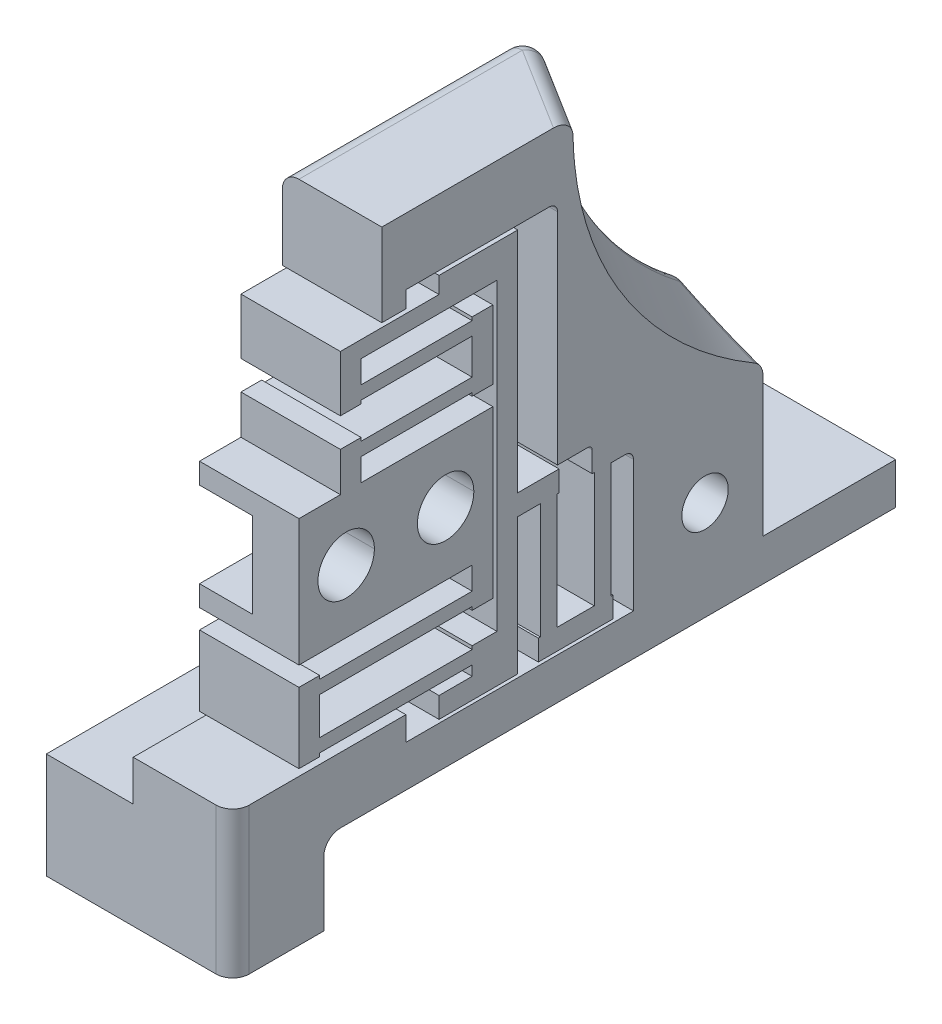
SolidWorks part; units mm, degrees
other "Markup1"
sketch "Sketch8" plane through (10.5, 0, 3) normal (0.7095, 0.0467, 0.7031) x (0.7044, -0.0184, -0.7096)
ref_plane "Front Plane" through (0, 0, 0) normal (0, 0, 1) x (1, 0, 0)
ref_plane "Top Plane" through (0, 0, 0) normal (0, 1, 0) x (1, 0, 0)
ref_plane "Right Plane" through (0, 0, 0) normal (1, 0, 0) x (0, 0, -1)
sketch "Sketch1" plane through (0, 0, 0) normal (1, 0, 0) x (0, 0, -1)
  line L0 (-1.25, -12.7333) -> (6.7, -12.7333)
  line L1 (6.7, -12.7333) -> (6.7, -22.75)
  line L2 (-5, -12.7333) -> (-5, -20.3833)
  line L3 (-5, -20.3833) -> (5.45, -20.3833)
  line L57 (-3.75, -22.55) -> (-3.75, -24.8)
  line L58 (-3.75, -24.8) -> (5.45, -24.8)
  line L60 (5.45, -20.3833) -> (5.45, -21.75)
  line L62 (-5, -21.55) -> (-5, -25.8)
  line L64 (6.95, -6.25) -> (6.95, -24.6)
  line L65 (-1.25, -11.3667) -> (5.45, -11.3667)
  line L66 (5.45, -10.5667) -> (5.45, -8.4167)
  line L68 (-2.5, -8.6167) -> (-2.5, -5.25)
  line L69 (-1.25, -12.7333) -> (-1.25, -11.3667)
  line L71 (6.7, -11.5667) -> (6.7, -7.4167)
  line L73 (-1.25, -7.6167) -> (-1.25, -6.25)
  line L74 (-1.25, -6.25) -> (6.95, -6.25)
  line L75 (-2.5, -5.25) -> (3.45, -5.25)
  line L79 (5.45, -11.3667) -> (5.45, -11.5667)
  line L80 (5.45, -11.5667) -> (6.7, -11.5667)
  line L85 (5.45, -10.5667) -> (-1.25, -10.5667)
  line L86 (-1.25, -10.5667) -> (-1.25, -10.3667)
  line L87 (-1.25, -10.3667) -> (-2.5, -10.3667)
  line L90 (5.45, -8.4167) -> (-1.25, -8.4167)
  line L91 (-1.25, -8.4167) -> (-1.25, -8.6167)
  line L92 (-1.25, -8.6167) -> (-2.5, -8.6167)
  line L93 (-1.25, -7.6167) -> (5.45, -7.6167)
  line L98 (5.45, -7.6167) -> (5.45, -7.4167)
  line L99 (5.45, -7.4167) -> (6.7, -7.4167)
  line L102 (5.45, -21.75) -> (-3.75, -21.75)
  line L103 (-3.75, -21.75) -> (-3.75, -21.55)
  line L104 (-3.75, -21.55) -> (-5, -21.55)
  line L105 (6.7, -22.75) -> (5.45, -22.75)
  line L106 (5.45, -22.75) -> (5.45, -22.55)
  line L111 (5.45, -22.55) -> (-3.75, -22.55)
  line L115 (5.45, -24.8) -> (5.45, -24.6)
  line L116 (5.45, -24.6) -> (6.95, -24.6)
  line L117 (-5, -25.8) -> (-3.75, -25.8)
  line L118 (-3.75, -25.8) -> (-3.75, -25.6)
  line L119 (-3.75, -25.6) -> (5.45, -25.6)
  line L124 (5.45, -25.6) -> (5.45, -26.2)
  line L126 (5.45, -26.2) -> (3.45, -26.2)
  line L127 (3.45, -26.2) -> (3.45, -27.45)
  line L128 (3.45, -27.45) -> (8.2, -27.45)
  line L130 (12.8167, -26.2) -> (10.5667, -26.2)
  line L131 (10.5667, -26.2) -> (10.5667, -19.2333)
  line L136 (10.5667, -19.2333) -> (10.6917, -19.2333)
  line L141 (12.8167, -19.2333) -> (12.8167, -26.2)
  line L145 (9.5667, -26.2) -> (9.4417, -26.2)
  line L146 (9.5667, -26.2) -> (9.5667, -19.2333)
  line L150 (9.5667, -19.2333) -> (8.2, -19.2333)
  line L153 (8.2, -17.9833) -> (10.6917, -17.9833)
  line L155 (14.6833, -19.2333) -> (13.8167, -19.2333)
  line L160 (13.8167, -19.2333) -> (13.8167, -26.2)
  line L168 (15.1833, -27.7) -> (15.1833, -19.7333)
  line L179 (15.1833, -27.7) -> (1.45, -27.7)
  line L180 (1.45, -27.7) -> (1.45, -26.2)
  line L181 (1.45, -26.2) -> (-9, -26.2)
  line L184 (-9, -30.15) -> (23, -30.15)
  line L187 (23, 0) -> (0, 0)
  line L189 (8.2, -27.45) -> (8.2, -19.2333)
  line L190 (1.45, -5) -> (0, -5)
  line L191 (0, -5) -> (0, 0)
  line L192 (13.9417, -26.2) -> (13.8167, -26.2)
  line L193 (12.4417, -17.7333) -> (10.6, -17.7333)
  line L194 (10.6, -17.7333) -> (10.6, -4.5)
  line L198 (9.4417, -26.2) -> (9.4417, -27.45)
  line L199 (13.9417, -26.2) -> (13.9417, -27.45)
  line L200 (13.9417, -27.45) -> (9.4417, -27.45)
  line L201 (8.2, -17.9833) -> (8.2, -4.25)
  line L203 (12.6917, -19.2333) -> (12.6917, -17.9833)
  line L204 (10.6917, -19.2333) -> (10.6917, -17.9833)
  line L205 (12.6917, -19.2333) -> (12.8167, -19.2333)
  line L212 (-9, -30.15) -> (-9, -26.2)
  line L214 (-2.5, -12.7333) -> (-5, -12.7333)
  line L215 (-2.5, -12.7333) -> (-2.5, -10.3667)
  line L216 (23, 0) -> (23, -30.15)
  line L217 (1.45, -5) -> (1.45, -4)
  line L218 (1.45, -4) -> (10.1, -4)
  line L219 (3.45, -5.25) -> (3.45, -4.25)
  line L220 (3.45, -4.25) -> (8.2, -4.25)
  line L221 (13.8167, -19.2333) -> (15.1833, -19.2333) construction
  arc A4 (14.6833, -19.2333) -> (15.1833, -19.7333) centre (14.6833, -19.7333) cw
  arc A5 (12.6917, -17.9833) -> (12.4417, -17.7333) centre (12.4417, -17.9833) ccw
  arc A6 (10.1, -4) -> (10.6, -4.5) centre (10.1, -4.5) cw
  circle A7 centre (3.85, -16.5583) radius 1.7
  circle A8 centre (-2.15, -16.5583) radius 1.7
  circle A9 centre (-2.15, -16.5583) radius 2.85 construction
  circle A10 centre (3.85, -16.5583) radius 2.85 construction
  point P120 (10.6, -5)
  point P140 (15.1833, -19.2333)
  point P144 (12.6917, -17.7333)
  point P151 (-5, -16.5583)
  point P159 (-1.875, -8.6167)
  dimension "D61" = 0.5
  dimension "D62" = 0.25
  dimension "D66" = 0.5
  dimension "D67" = 3.4
  dimension "D68" = 5.7
  dimension "D3" = 4.25
  dimension "D4" = 0.2
  dimension "D6" = 0.8
  dimension "D9" = 0.8
  dimension "D10" = 1.1667
  dimension "D17" = 0.8
  dimension "D18" = 1.75
  dimension "D21" = 0.8
  dimension "D23" = 1
  dimension "D24" = 0.25
  dimension "D37" = 1.25
  dimension "D40" = 0.25
  dimension "D44" = 1
  dimension "D12" = 7.65
  dimension "D20" = 1.25
  dimension "D26" = 1.25
  dimension "D28" = 0.25
  dimension "D33" = 1.25
  dimension "D49" = 2.4
  dimension "D50" = 0.25
  dimension "D31" = 5
  dimension "D54" = 5
  dimension "D55" = 1.25
  dimension "D65" = 2.5
  dimension "D64" = 2.5
  dimension "D29" = 2
  dimension "D52" = 0.25
  dimension "D56" = 1
  dimension "D69" = 6
  dimension "D39" = 4
  dimension "D51" = 32
  dimension "D22" = 1.1667
  dimension "D53" = 2
  dimension "D19" = 0.2
  dimension "D7" = 0.4
  dimension "D8" = 1.45
  dimension "D11" = 1
  dimension "D13" = 4.5
  dimension "D14" = 2
  dimension "D15" = 30.15
  dimension "D16" = 1.25
  dimension "D25" = 1.25
extrude "Boss-Extrude1" add sketch "Sketch1" along normal blind 6
sketch "Sketch2" plane through (0, 0, 5) normal (0, 0, 1) x (1, 0, 0)
  line L0 (6, -12.7333) -> (6, -20.3833) construction
  line L1 (6, -19.1333) -> (2.8, -19.1333)
  line L2 (6, -19.1333) -> (6, -13.9833)
  line L3 (6, -13.9833) -> (2.8, -13.9833)
  line L4 (2.8, -19.1333) -> (2.8, -13.9833)
  line L5 (6, -12.7333) -> (6, -20.3833) construction
  dimension "D1" = 3.2
  dimension "D2" = 1.25
  dimension "D3" = 1.25
extrude "Cut-Extrude4" cut sketch "Sketch2" against normal up to next
sketch "Sketch3" plane through (0, -30.15, 0) normal (0, -1, 0) x (1, 0, 0)
  line L0 (11.24, -4.18) -> (16.24, -4.18)
  line L1 (0, -31) -> (16.24, -31)
  line L2 (0, -31) -> (0, 9)
  line L4 (11.24, -4.18) -> (11.24, 9)
  line L5 (6, 9) -> (6, -23) construction
  line L7 (16.24, -31) -> (16.24, -4.18)
  line L8 (0, 9) -> (0, -23) construction
  line L9 (11.24, 9) -> (0, 9)
  circle A0 centre (8.6, -7.73) radius 1.6
  circle A1 centre (8.6, -19.73) radius 1.6
  dimension "D3" = 3.2
  dimension "D1" = 13.18
  dimension "D2" = 2.6
  dimension "D4" = 12
  dimension "D5" = 5
  dimension "D6" = 40
  dimension "D7" = 16.73
  dimension "D8" = 11.24
sketch "Sketch7" plane through (0, 0, 0) normal (-1, 0, 0) x (0, 0, 1)
  line L0 (2.5, -12.7333) -> (5, -12.7333) construction
  line L2 (-6.7, -12.7333) -> (-6.7, -22.75) construction
  circle A0 centre (2.15, -16.6083) radius 1.7
  circle A1 centre (-3.85, -16.6083) radius 1.7
  circle A2 centre (2.15, -16.6083) radius 2.85 construction
  circle A3 centre (-3.85, -16.6083) radius 2.85 construction
  dimension "D1" = 3.4
  dimension "D2" = 3.875
  dimension "D5" = 5.7
  dimension "D3" = 6
extrude "Cut-Extrude3" cut sketch "Sketch7" against normal up to next
extrude "Boss-Extrude2" add sketch "Sketch3" against normal blind 2.5
sketch "Sketch12" plane through (0, 0, 9) normal (0, 0, 1) x (1, 0, 0)
  line L0 (6, -26.2) -> (6, -27.65) construction
  line L1 (11.24, -27.65) -> (6, -27.65)
  line L2 (11.24, -27.65) -> (11.24, -28.65)
  line L3 (11.24, -28.65) -> (6, -28.65)
  line L4 (6, -27.65) -> (6, -28.65)
  line L5 (11.24, -27.65) -> (6, -27.65) construction
  dimension "D1" = 1
  dimension "D2" = 5.24
extrude "Cut-Extrude6" cut sketch "Sketch12" against normal blind 35.15
sketch "Sketch14" plane through (0, 0, 0) normal (-1, 0, 0) x (0, 0, 1)
  line L1 (9, -28.7) -> (3.5, -28.7)
  line L2 (9, -28.7) -> (9, -35.03)
  line L3 (9, -35.03) -> (3.5, -35.03)
  line L4 (3.5, -28.7) -> (3.5, -35.03)
  line L5 (-1.45, -26.2) -> (9, -26.2) construction
  line L6 (9, -26.2) -> (9, -30.15) construction
  dimension "D1" = 2.5
  dimension "D2" = 6.33
  dimension "D3" = 5.5
extrude "Boss-Extrude4" add sketch "Sketch14" against normal blind 11.24
sketch "Sketch15" plane through (11.24, 0, 0) normal (1, 0, 0) x (0, 0, -1)
  line L1 (-3.5, -30.15) -> (-7.5, -30.15)
  line L2 (-3.5, -30.15) -> (-3.5, -33.48)
  line L3 (-3.5, -33.48) -> (-7.5, -33.48)
  line L4 (-7.5, -30.15) -> (-7.5, -33.48)
  dimension "D1" = 4
  dimension "D2" = 3.33
extrude "Cut-Extrude7" cut sketch "Sketch15" against normal blind 10.25
ref_plane "Plane2" through (0, 0, 7.1) normal (0, 0, 1) x (1, 0, 0)
ref_axis "Axis1" through (11.24, 27.1504, 7.1) along (0, -1, 0)
mirror "Mirror1" [suppressed] of bodies 111
delete or keep bodies "Body-Delete/Keep 1" [suppressed] type delete bodies bodies 111
ref_plane "Plane1" through (4.8929, 0, -3.0574) normal (-0.848, 0, 0.5299) x (0, -1, 0)
sketch "Sketch10" plane through (4.8929, 0, -3.0574) normal (-0.848, 0, 0.5299) x (0, -1, 0)
  line L0 (30.15, 13.5887) -> (30.15, 7.6324) construction
  line L1 (30.15, 2.9682) -> (30.15, -26.2895) construction
  line L2 (30.15, 12.3167) -> (30.15, -33.4435) construction
  circle A0 centre (0.65, -31.2799) radius 21.5
  dimension "D2" = 43
  dimension "D1" = 43.5966
  dimension "D3" = 29.5
extrude "Cut-Extrude5" cut sketch "Sketch10" against normal blind 25
fillet "Fillet1" radius 1 9 edges at (3.1138, -17.4436, -23) (3, 0, -13.4184) (6, -21.8736, -23) (6, -8.7382, -17.1438) (6, 0, -7.6465) (16.24, -28.9, -4.18) (0.99, -31.815, 7.5) (0, -30.615, 9) (0.495, -30.15, 3.5)
chamfer "Chamfer1" distance 1 angle 45 1 edges at (11.24, -27.65, -15.165)
delete or keep bodies "Body-Delete/Keep 2" [suppressed] type delete bodies bodies 113
sketch "Sketch16" plane through (0, 0, 0) normal (-1, 0, 0) x (0, 0, 1)
  line L0 (-23, -27.65) -> (-31, -27.65) construction
  line L1 (-23, -27.65) -> (-23, -19.2756) construction
  circle A0 centre (-19.5, -24.15) radius 1.4
  dimension "D1" = 2.8
  dimension "D2" = 3.5
  dimension "D3" = 3.5
extrude "Cut-Extrude8" cut sketch "Sketch16" against normal through all
sketch "Sketch17" plane through (0, 0, 9) normal (0, 0, 1) x (1, 0, 0)
  line L1 (11.24, -30.15) -> (16.24, -30.15)
  line L2 (11.24, -30.15) -> (11.24, -27.65)
  line L3 (11.24, -27.65) -> (16.24, -27.65)
  line L4 (16.24, -30.15) -> (16.24, -27.65)
extrude "Cut-Extrude9" cut sketch "Sketch17" against normal through all
mirror "Mirror2" about plane through (0, -19.7333, -14.6833) normal (-1, 0, 0) of bodies 124 113
delete or keep bodies "Body-Delete/Keep 3" type keep bodies bodies 114
equation "\"VerticalFlexureWidth\"= 0.8"
equation "\"VerticalFlexureGap\"= 1"
equation "\"VerticalDoubleFlexureWidth\"= 2 * \"VerticalFlexureWidth\" + \"VerticalFlexureGap\""
equation "\"HorizontalFlexureLength\"= 7"
equation "\"FlexureJointWidth\"= 1.25"
equation "\"HeadHeight\"= 7.5"
equation "\"VerticalFlexureLength\"= 18"
equation "\"MinGap\"=0.25"
equation "\"BaseplateHeight+Tolerance\"= 3.33"
equation "\"HeadWidth\"= 13"
equation "\"HorizontalFlexureWidth\"= 1"
equation "\"HorizontalFlexureGap\"= 1"
equation "\"HorizontalDoubleFlexureWidth\"= 2 * \"HorizontalFlexureWidth\" + \"HorizontalFlexureGap\""
equation "\"FlexureWidth\"=0.85"
equation "\"FlexureWideWidth\"= 1.25"
equation "\"FlexureGap\"=1.75"
equation "\"TwinFlexureWidth\"= \"FlexureGap\" + 2 * \"FlexureWideWidth\""
equation "\"D3@Sketch1\"=\"TwinFlexureWidth\""
equation "\"FlexureNeckWidth\"= ( \"FlexureWideWidth\" - \"FlexureWidth\" ) / 2"
equation "\"D4@Sketch1\"=\"FlexureNeckWidth\""
equation "\"D6@Sketch1\"=\"VerticalFlexureWidth\""
equation "\"D9@Sketch1\"=\"VerticalFlexureWidth\""
equation "\"D10@Sketch1\"=\"FlexureGapEdge\""
equation "\"D21@Sketch1\"=\"VerticalFlexureWidth\""
equation "\"D18@Sketch1\"=\"FlexureGap\""
equation "\"FlexureLength\"= 2"
equation "\"MainSupport\"=1.5"
equation "\"D24@Sketch1\"=\"MinGap\""
equation "\"D37@Sketch1\"=\"FlexureJointWidth\""
equation "\"D40@Sketch1\"=\"MinGap\""
equation "\"D44@Sketch1\"=\"HorizontalFlexureWidth\""
equation "\"D20@Sketch1\"=\"MainSupport\"-0.25"
equation "\"D26@Sketch1\"=\"FlexureJointWidth\""
equation "\"D28@Sketch1\"=\"MinGap\""
equation "\"D33@Sketch1\"=\"FlexureJointWidth\""
equation "\"FlexureGapEdge\"= \"FlexureGap\" * ( 2 / 3 )"
equation "\"D55@Sketch1\"=\"FlexureJointWidth\""
equation "\"FlexurePlateConnectionHeigh\"= 5.15 + 2.5"
equation "\"D12@Sketch1\"=\"FlexurePlateConnectionHeigh\""
equation "\"D52@Sketch1\"=\"MinGap\""
equation "\"D17@Sketch1\"=\"VerticalFlexureWidth\""
equation "\"D22@Sketch1\"=\"FlexureGapEdge\""
equation "\"D19@Sketch1\"=\"FlexureNeckWidth\""
equation "\"D11@Sketch1\"=\"HorizontalFlexureWidth\""
equation "\"D16@Sketch1\"=\"FlexureJointWidth\""
equation "\"D25@Sketch1\"=\"FlexureJointWidth\""
